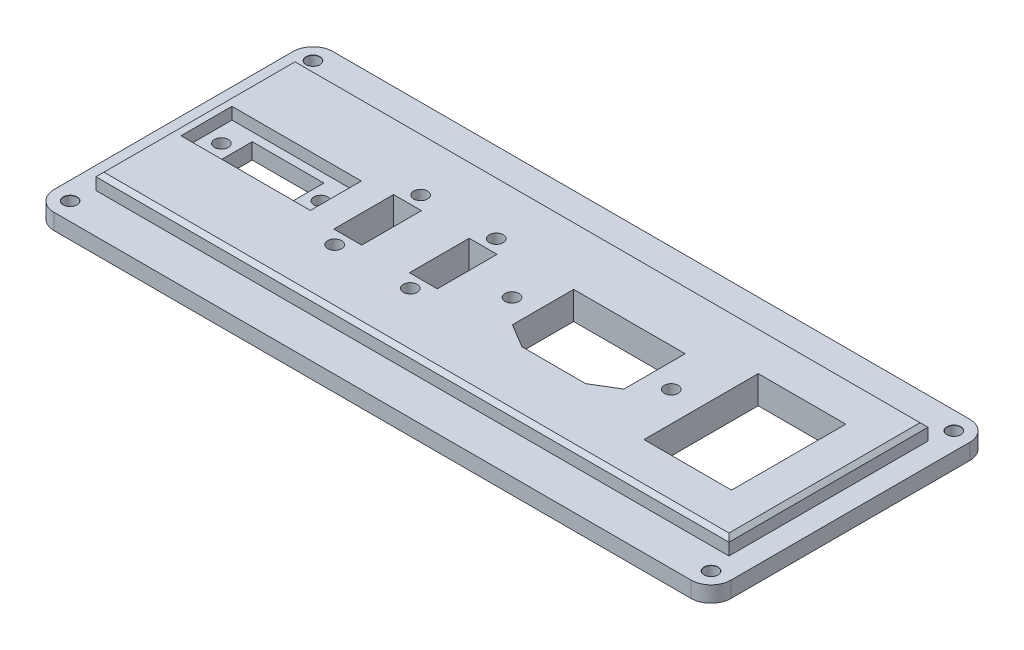
SolidWorks part; units mm, degrees
ref_plane "Front Plane" through (0, 0, 0) normal (0, 0, 1) x (1, 0, 0)
ref_plane "Top Plane" through (0, 0, 0) normal (0, 1, 0) x (1, 0, 0)
ref_plane "Right Plane" through (0, 0, 0) normal (1, 0, 0) x (0, 0, -1)
sketch "Sketch1" plane through (0, 0, 0) normal (0, 1, 0) x (1, 0, 0)
  line L1 (-85, 35) -> (85, 35)
  line L2 (-85, 35) -> (-85, -35)
  line L3 (-85, -35) -> (85, -35)
  line L4 (85, 35) -> (85, -35)
  line L5 (-85, 35) -> (85, -35) construction
  line L6 (-85, -35) -> (85, 35) construction
  point P0 (0, 0)
  dimension "D1" = 70
  dimension "D2" = 170
extrude "Boss-Extrude1" add sketch "Sketch1" along normal blind 4
sketch "Sketch2" plane through (0, 4, 0) normal (0, 1, 0) x (1, 0, 0)
  line L0 (85, 35) -> (-85, 35) construction
  line L1 (-79.5, -25) -> (79.5, -25)
  line L2 (-79.5, -25) -> (-79.5, 25)
  line L3 (-79.5, 25) -> (79.5, 25)
  line L4 (79.5, -25) -> (79.5, 25)
  line L5 (-79.5, -25) -> (79.5, 25) construction
  line L6 (-79.5, 25) -> (79.5, -25) construction
  line L7 (85, -35) -> (85, 35) construction
  point P0 (0, 0)
  dimension "D1" = 10
  dimension "D2" = 5.5
extrude "Boss-Extrude2" add sketch "Sketch2" along normal blind 4 contours L3 L4 L1 L2
hole_wizard "M3 Clearance Hole1" positions "Sketch3" profile "Sketch5" hole size "M3" standard "ISO" end condition through all
sketch "Sketch3" plane through (0, 4, 0) normal (0, 1, 0) x (1, 0, 0)
  line L23 (80.5, -30.5) -> (80.5, 30.5)
  line L24 (-80.5, -30.5) -> (80.5, -30.5)
  line L25 (-80.5, 30.5) -> (-80.5, -30.5)
  line L26 (80.5, 30.5) -> (-80.5, 30.5)
  line L27 (80.5, -30.5) -> (80.5, 30.5)
  line L28 (-80.5, -30.5) -> (80.5, -30.5)
  line L29 (-80.5, 30.5) -> (-80.5, -30.5)
  line L30 (80.5, 30.5) -> (-80.5, 30.5)
  point P46 (80.5, -30.5)
  point P47 (80.5, 30.5)
  point P48 (-80.5, -30.5)
  point P49 (-80.5, 30.5)
  dimension "D1" = 4.5
sketch "Sketch5" plane through (80.5, 4, 30.5) normal (1, 0, 0) x (0, 0, 1)
  line L0 (0, 0) -> (0, 4)
  line L1 (0, 4) -> (1.7, 4)
  line L2 (1.7, 4) -> (1.7, 0.05)
  line L3 (1.7, 0.05) -> (1.75, 0)
  line L5 (1.75, 0) -> (0, 0)
  line L6 (-1.7, 0.05) -> (-1.75, 0) construction
  line L11 (0, -6.35) -> (0, 107.95) construction
  dimension "Thru Hole Dia." = 3.4
  dimension "Thru Hole Depth" = 4
  dimension "Near C'Sink Dia." = 3.5
  dimension "Near C'Sink Angle" = 90
sketch "Sketch6" plane through (0, 0, 0) normal (0, -1, 0) x (1, 0, 0)
  line L0 (-73, 0) -> (-48, 0) construction
  line L1 (47.5, 14.35) -> (69.5, 14.35)
  line L2 (47.5, 14.35) -> (47.5, -14.35)
  line L3 (47.5, -14.35) -> (69.5, -14.35)
  line L4 (69.5, 14.35) -> (69.5, -14.35)
  line L5 (47.5, 14.35) -> (69.5, -14.35) construction
  line L6 (47.5, -14.35) -> (69.5, 14.35) construction
  line L7 (-69.5, 4.25) -> (-51.5, 4.25)
  line L8 (-69.5, 4.25) -> (-69.5, -4.25)
  line L9 (-69.5, -4.25) -> (-51.5, -4.25)
  line L10 (-79.5, 25) -> (-79.5, -25)
  line L11 (79.5, 25) -> (-79.5, 25)
  line L12 (79.5, -25) -> (79.5, 25)
  line L13 (-79.5, -25) -> (79.5, -25)
  line L14 (-79.5, 25) -> (-79.5, -25) construction
  line L15 (79.5, 25) -> (-79.5, 25) construction
  line L16 (79.5, -25) -> (79.5, 25) construction
  line L17 (-79.5, -25) -> (79.5, -25) construction
  line L18 (-51.5, 4.25) -> (-51.5, -4.25)
  line L19 (-69.5, 4.25) -> (-51.5, -4.25) construction
  line L20 (-69.5, -4.25) -> (-51.5, 4.25) construction
  line L21 (20, -9.5) -> (20, 9.5) construction
  line L22 (-76.75, -6.4) -> (-44.25, -6.4)
  line L23 (-76.75, -6.4) -> (-76.75, 6.4)
  line L24 (-76.75, 6.4) -> (-44.25, 6.4)
  line L25 (-44.25, -6.4) -> (-44.25, 6.4)
  line L26 (-76.75, -6.4) -> (-44.25, 6.4) construction
  line L27 (-76.75, 6.4) -> (-44.25, -6.4) construction
  line L28 (12, 9.5) -> (28, 9.5)
  line L29 (28, 9.5) -> (34, 5.8944)
  line L30 (34, 5.8944) -> (34, -9.5)
  line L31 (34, -9.5) -> (6, -9.5)
  line L32 (6, 5.8944) -> (6, -9.5)
  line L33 (12, 9.5) -> (6, 5.8944)
  line L34 (-33.75, 10.8) -> (-33.75, -10.8) construction
  line L35 (-39.25, 14.5) -> (-28.25, 14.5)
  line L36 (-39.25, 14.5) -> (-39.25, -14.5)
  line L37 (-39.25, -14.5) -> (-28.25, -14.5)
  line L38 (-28.25, 14.5) -> (-28.25, -14.5)
  line L39 (-39.25, 14.5) -> (-28.25, -14.5) construction
  line L40 (-39.25, -14.5) -> (-28.25, 14.5) construction
  line L41 (-20.25, 14.5) -> (-9.25, 14.5)
  line L42 (-20.25, 14.5) -> (-20.25, -14.5)
  line L43 (-20.25, -14.5) -> (-9.25, -14.5)
  line L44 (-9.25, 14.5) -> (-9.25, -14.5)
  line L45 (-20.25, 14.5) -> (-9.25, -14.5) construction
  line L46 (-20.25, -14.5) -> (-9.25, 14.5) construction
  line L47 (-37.25, -7.5) -> (-30.25, -7.5)
  line L48 (-37.25, -7.5) -> (-37.25, 7.5)
  line L49 (-37.25, 7.5) -> (-30.25, 7.5)
  line L50 (-30.25, -7.5) -> (-30.25, 7.5)
  line L51 (-37.25, -7.5) -> (-30.25, 7.5) construction
  line L52 (-37.25, 7.5) -> (-30.25, -7.5) construction
  line L53 (-18.25, -7.5) -> (-11.25, -7.5)
  line L54 (-18.25, -7.5) -> (-18.25, 7.5)
  line L55 (-18.25, 7.5) -> (-11.25, 7.5)
  line L56 (-11.25, -7.5) -> (-11.25, 7.5)
  line L57 (-18.25, -7.5) -> (-11.25, 7.5) construction
  line L58 (-18.25, 7.5) -> (-11.25, -7.5) construction
  line L59 (-14.75, 10.8) -> (-14.75, -10.8) construction
  circle A0 centre (-73, 0) radius 1.75
  circle A1 centre (-48, 0) radius 1.75
  circle A2 centre (0, 0) radius 1.75
  circle A3 centre (40, 0) radius 1.75
  circle A4 centre (-14.75, -10.8) radius 2.8 construction
  circle A5 centre (-14.75, 10.8) radius 2.8 construction
  circle A6 centre (-33.75, 10.8) radius 2.8 construction
  circle A7 centre (-33.75, -10.8) radius 2.8 construction
  circle A8 centre (-14.75, 10.8) radius 1.75
  circle A9 centre (-33.75, 10.8) radius 1.75
  circle A10 centre (-14.75, -10.8) radius 1.75
  circle A11 centre (-33.75, -10.8) radius 1.75
  point P0 (58.5, 0)
  point P8 (-60.5, 0)
  point P19 (-60.5, 0)
  point P20 (-60.5, 0)
  point P27 (-14.75, 0)
  point P32 (20, 0)
  point P42 (-33.75, 0)
  point P48 (-33.75, 0)
  point P53 (-14.75, 0)
  point P66 (-14.75, 0)
  point P67 (-33.75, 0)
  dimension "D8" = 3.5
  dimension "D13" = 3.5
  dimension "D26" = 5.6
  dimension "D1" = 22
  dimension "D2" = 28.7
  dimension "D4" = 10
  dimension "D5" = 18
  dimension "D6" = 8.5
  dimension "D7" = 10
  dimension "D9" = 25
  dimension "D10" = 28
  dimension "D11" = 19
  dimension "D12" = 40
  dimension "D14" = 16
  dimension "D15" = 20
  dimension "D16" = 7
  dimension "D17" = 11
  dimension "D18" = 11
  dimension "D19" = 29
  dimension "D20" = 5
  dimension "D21" = 8
  dimension "D22" = 15
  dimension "D23" = 7
  dimension "D24" = 32.5
  dimension "D25" = 12.8
  dimension "D27" = 16
  dimension "D3" = 0
extrude "Cut-Extrude1" cut sketch "Sketch6" against normal through all contours A1 | A0 | L18 L7 L8 L9 | A9 | A11 | A8 | A10 | A2 | L4 L1 L2 L3 | L47 L50 L49 L48 | L53 L56 L55 L54 | L29 L30 L31 L32 L33 L28 | A3 region at (58.5, 0, 0) region at (-60.5, 0, 0) region at (-33.75, 0, 0) region at (-14.75, 0, 0) region at (-73, 0, 0) region at (-48, 0, 0) region at (0, 0, 0) region at (-14.75, 0, 10.8) region at (-33.75, 0, 10.8) region at (-14.75, 0, -10.8) region at (-33.75, 0, -10.8)
extrude "Cut-Extrude2" cut sketch "Sketch6<3>" along normal offset from surface (3 mm away) 5 from surface contours L18 L7 L8 L9 | L9 L18 L7 L8 | L22 L25 L24 L23 region at (-60.5, 0, 0) up to face at (-73, 0, -1.75) starting at face at (-73, 8, -1.75)
sketch "Sketch6<3>" plane through (0, 0, 0) normal (0, -1, 0) x (1, 0, 0) same geometry as "Sketch6"
chamfer "Chamfer1" distance 1 angle 45 26 edges at (-79.5, 8, 0) (0, 8, -25) (79.5, 8, 0) (0, 8, 25) (58.5, 0, -14.35) (69.5, 0, 0) (47.5, 0, 0) (58.5, 0, 14.35) (9, 0, 7.6972) (6, 0, -1.8028) (20, 0, -9.5) (34, 0, -1.8028) (31, 0, 7.6972) (20, 0, 9.5) (-14.75, 0, -7.5) (-11.25, 0, 0) (-18.25, 0, 0) (-14.75, 0, 7.5) (-33.75, 0, -7.5) (-30.25, 0, 0) (-37.25, 0, 0) (-33.75, 0, 7.5) (-51.5, 0, 0) (-60.5, 0, 4.25) (-69.5, 0, 0) (-60.5, 0, -4.25)
fillet "Fillet1" radius 5 4 edges at (-85, 2, 35) (-85, 2, -35) (85, 2, -35) (85, 2, 35)
equation "\"D13@Sketch6\"=\"D8@Sketch6\""
